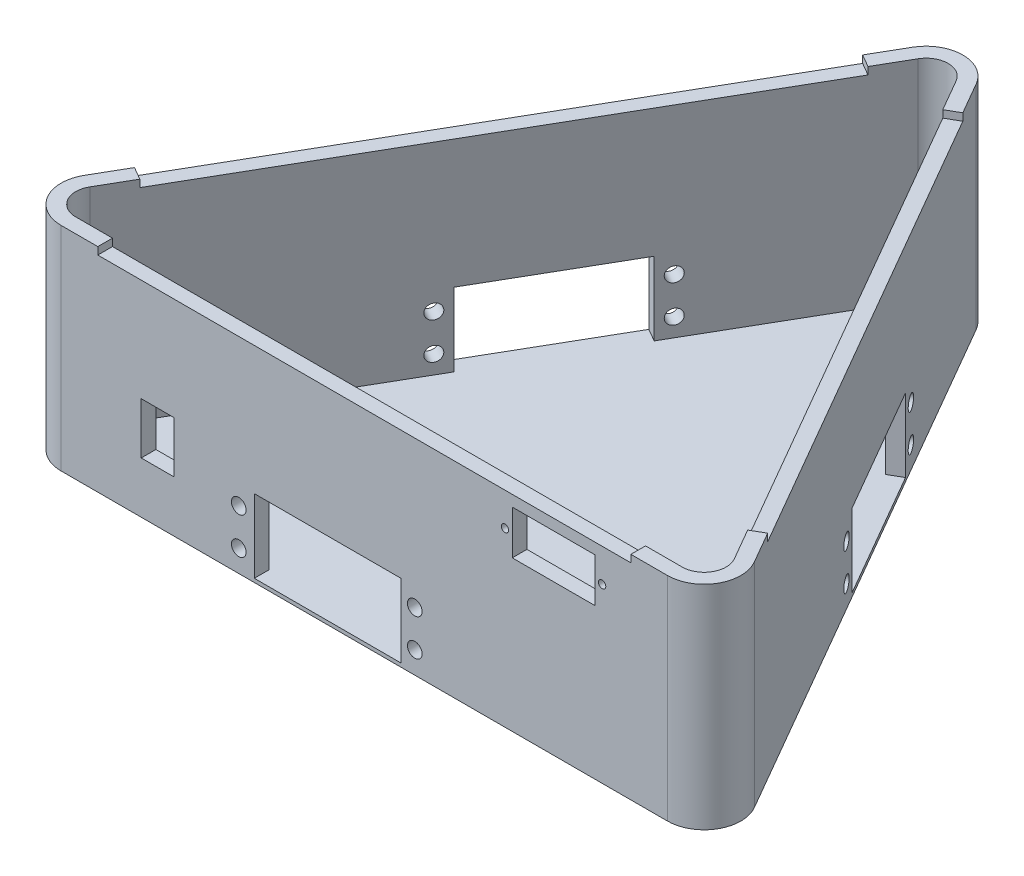
SolidWorks part; units mm, degrees
ref_plane "Front Plane" through (0, 0, 0) normal (0, 0, 1) x (1, 0, 0)
ref_plane "Top Plane" through (0, 0, 0) normal (0, 1, 0) x (1, 0, 0)
ref_plane "Right Plane" through (0, 0, 0) normal (1, 0, 0) x (0, 0, -1)
sketch "Sketch2" plane through (0, 0, 0) normal (0, 1, 0) x (1, 0, 0)
  line L0 (0, 0) -> (0, 115.4701) construction
  line L1 (-5.1962, 98.4701) -> (-87.8756, -44.735)
  line L2 (-8.6603, 100.4701) -> (-91.3397, -42.735)
  line L3 (-82.6795, -57.735) -> (82.6795, -57.735)
  line L4 (91.3397, -42.735) -> (8.6603, 100.4701)
  line L5 (-82.6795, -53.735) -> (82.6795, -53.735)
  line L6 (87.8756, -44.735) -> (5.1962, 98.4701)
  line L7 (0, 0) -> (-100, -57.735) construction
  line L8 (0, 0) -> (100, -57.735) construction
  circle A0 centre (0, 0) radius 57.735 construction
  arc A1 (82.6795, -57.735) -> (91.3397, -42.735) centre (82.6795, -47.735) ccw
  arc A2 (-91.3397, -42.735) -> (-82.6795, -57.735) centre (-82.6795, -47.735) ccw
  arc A3 (8.6603, 100.4701) -> (-8.6603, 100.4701) centre (0, 95.4701) ccw
  arc A4 (-87.8756, -44.735) -> (-82.6795, -53.735) centre (-82.6795, -47.735) ccw
  arc A5 (82.6795, -53.735) -> (87.8756, -44.735) centre (82.6795, -47.735) ccw
  arc A6 (5.1962, 98.4701) -> (-5.1962, 98.4701) centre (0, 95.4701) ccw
  point P9 (100, -57.735)
  point P12 (-100, -57.735)
  dimension "D2" = 10
  dimension "D1" = 200
  dimension "D3" = 4
extrude "Boss-Extrude1" add sketch "Sketch2" against normal blind 1 contours L2 A2 L3 A1 L4 A3
extrude "Boss-Extrude2" add sketch "Sketch2<6>" along normal blind 55
sketch "Sketch2<6>" plane through (0, 0, 0) normal (0, 1, 0) x (1, 0, 0) same geometry as "Sketch2"
sketch "Sketch3" plane through (0, 0, 57.735) normal (0, 0, 1) x (1, 0, 0)
  line L0 (-82.6795, 0) -> (82.6795, 0) construction
  line L1 (-30, 10) -> (10, 10) construction
  line L2 (0, 0) -> (0, 10) construction
  line L3 (-82.6795, -1) -> (-82.6795, 55) construction
  line L8 (82.6795, -1) -> (82.6795, 55) construction
  line L9 (-82.6795, 0) -> (-82.6795, 20) construction
  line L10 (-82.6795, 20) -> (82.6795, 20) construction
  line L11 (82.6795, 20) -> (82.6795, 0) construction
  line L12 (-82.6795, 20) -> (82.6795, 20) construction
  line L13 (46.3397, 52) -> (46.3397, 46) construction
  line L22 (-30, 20) -> (10, 20)
  line L23 (-30, 20) -> (-30, 0)
  line L24 (-30, 0) -> (10, 0)
  line L25 (10, 20) -> (10, 0)
  line L26 (-34.2428, 15) -> (13.7572, 15) construction
  line L27 (-30, 10) -> (-82.6795, 10) construction
  line L28 (-82.6795, 20) -> (-82.6795, 0) construction
  line L29 (40.3397, 46) -> (40.3397, 52) construction
  line L30 (40.3397, 40) -> (62.8397, 40)
  line L31 (40.3397, 52) -> (62.8397, 52)
  line L32 (40.3397, 52) -> (40.3397, 40)
  line L34 (62.8397, 52) -> (62.8397, 40)
  line L39 (-60.8397, 27) -> (-51.8397, 27)
  line L40 (-60.8397, 27) -> (-60.8397, 13)
  line L41 (-60.8397, 13) -> (-51.8397, 13)
  line L42 (-51.8397, 27) -> (-51.8397, 13)
  line L43 (-60.8397, 27) -> (-51.8397, 13) construction
  line L44 (-60.8397, 13) -> (-51.8397, 27) construction
  line L45 (10, 20) -> (10, 27) construction
  line L46 (-82.6795, -1) -> (82.6795, -1) construction
  line L49 (40.3397, 47.6468) -> (62.8397, 47.6468) construction
  circle A0 centre (-34.2428, 15) radius 2
  circle A1 centre (-34.2428, 5) radius 2
  circle A2 centre (13.7572, 15) radius 2
  circle A3 centre (13.7572, 5) radius 2
  circle A4 centre (38.3397, 46) radius 1
  circle A5 centre (64.8397, 46) radius 1
  point P21 (-56.3397, 20)
  point P37 (-10.2428, 10)
  point P40 (18, 10)
  point P43 (-30, 10)
  point P52 (51.5897, 46)
  dimension "D7" = 2
  dimension "D1" = 20
  dimension "D2" = 48
  dimension "D3" = 47
  dimension "D4" = 30
  dimension "D5" = 10
  dimension "D6" = 10
  dimension "D8" = 9
  dimension "D9" = 14
ref_axis "Axis1" through (0, 0, 0) along (0, 1, 0)
sketch "Sketch4" plane through (0, 55, 0) normal (0, 1, 0) x (1, 0, 0)
  line L0 (0, 105.4701) -> (0, 0) construction
  line L1 (0, 0) -> (-91.3397, -52.735) construction
  line L2 (0, 0) -> (91.3397, -52.735) construction
  line L3 (-8.6603, 100.4701) -> (-91.3397, -42.735) construction
  line L5 (0, 105.4701) -> (0, 101.4701)
  line L7 (-5.1962, 98.4701) -> (-87.8756, -44.735) construction
  line L12 (-10.1962, 89.8098) -> (-13.6603, 91.8098)
  line L13 (-13.6603, 91.8098) -> (-8.6603, 100.4701)
  line L16 (-82.8756, -36.0748) -> (-86.3397, -34.0748)
  line L17 (-86.3397, -34.0748) -> (-91.3397, -42.735)
  line L24 (-10.1962, 89.8098) -> (-5.1962, 98.4701)
  line L25 (-82.8756, -36.0748) -> (-87.8756, -44.735)
  line L29 (-91.3397, -52.735) -> (-87.8756, -50.735)
  arc A0 (8.6603, 100.4701) -> (-8.6603, 100.4701) centre (0, 95.4701) ccw construction
  arc A1 (-91.3397, -42.735) -> (-82.6795, -57.735) centre (-82.6795, -47.735) ccw construction
  arc A2 (82.6795, -57.735) -> (91.3397, -42.735) centre (82.6795, -47.735) ccw construction
  arc A5 (0, 105.4701) -> (-8.6603, 100.4701) centre (0, 95.4701) ccw
  arc A8 (0, 101.4701) -> (-5.1962, 98.4701) centre (0, 95.4701) ccw
  arc A9 (-87.8756, -44.735) -> (-87.8756, -50.735) centre (-82.6795, -47.735) ccw
  arc A12 (-91.3397, -42.735) -> (-91.3397, -52.735) centre (-82.6795, -47.735) ccw
  dimension "D2" = 10
  dimension "D3" = 10
extrude "Boss-Extrude3" add sketch "Sketch4" along normal blind 2 and the other way up to surface (55 mm away) other way up to face at (0, 0, 0)
extrude "Back" cut sketch "Sketch3" against normal blind 10
sketch "Sketch6" plane through (50, 0, -28.8675) normal (0.866, 0, -0.5) x (-0.5, 0, -0.866)
  line L0 (-82.6795, 0) -> (82.6795, 0) construction
  line L1 (-5.1962, 0) -> (-87.8756, 0) construction
  line L2 (-82.6795, -1) -> (-82.6795, 55) construction
  line L3 (0, 20) -> (0, 0) construction
  line L4 (-10, 10) -> (30, 10) construction
  line L5 (0, 10) -> (-10, 10) construction
  line L6 (0, 10) -> (30, 10) construction
  line L7 (-10, 0) -> (30, 0)
  line L12 (-10, 0) -> (-10, 20)
  line L13 (-10, 20) -> (30, 20)
  line L14 (30, 0) -> (30, 20)
  line L15 (-10, 10) -> (30, 10) construction
  circle A0 centre (-14, 15) radius 2
  circle A1 centre (-14, 5) radius 2
  circle A2 centre (34, 15) radius 2
  circle A3 centre (34, 5) radius 2
  point P21 (10, 10)
  point P22 (34, 10)
  point P25 (-10, 10)
  dimension "D1" = 20
  dimension "D2" = 10
  dimension "D3" = 30
  dimension "D4" = 48
  dimension "D6" = 10
extrude "Cut-Extrude3" cut sketch "Sketch6" against normal blind 10
sketch "Sketch7" plane through (-50, 0, -28.8675) normal (-0.866, 0, -0.5) x (-0.5, 0, 0.866)
  line L0 (-82.6795, 0) -> (82.6795, 0) construction
  line L1 (-82.6795, -1) -> (-82.6795, 57) construction
  line L2 (82.6795, -1) -> (82.6795, 57) construction
  line L3 (0, 0) -> (0, 20) construction
  line L4 (0, 0) -> (0, 77.7742) construction
  line L5 (0, 10) -> (-30, 10) construction
  line L6 (0, 10) -> (10, 10) construction
  line L7 (-10, 20) -> (-10, 0) construction
  line L8 (-30, 0) -> (10, 0)
  line L9 (-30, 0) -> (-30, 20)
  line L10 (-30, 20) -> (10, 20)
  line L11 (10, 0) -> (10, 20)
  line L12 (-34, 10) -> (14, 10) construction
  line L13 (-34, 15) -> (-34, 5) construction
  line L14 (14, 15) -> (14, 5) construction
  circle A0 centre (-34, 15) radius 2
  circle A1 centre (-34, 5) radius 2
  circle A2 centre (14, 15) radius 2
  circle A3 centre (14, 5) radius 2
  point P23 (-10, 10)
  point P26 (-34, 10)
  point P29 (14, 10)
  dimension "D1" = 10
  dimension "D2" = 48
  dimension "D3" = 10
  dimension "D4" = 10
extrude "Cut-Extrude4" cut sketch "Sketch7" against normal blind 10
pattern_circular "CirPattern1" count 3 every 120 about axis through (0, 0, 0) along (0, 1, 0) of "Boss-Extrude3"
